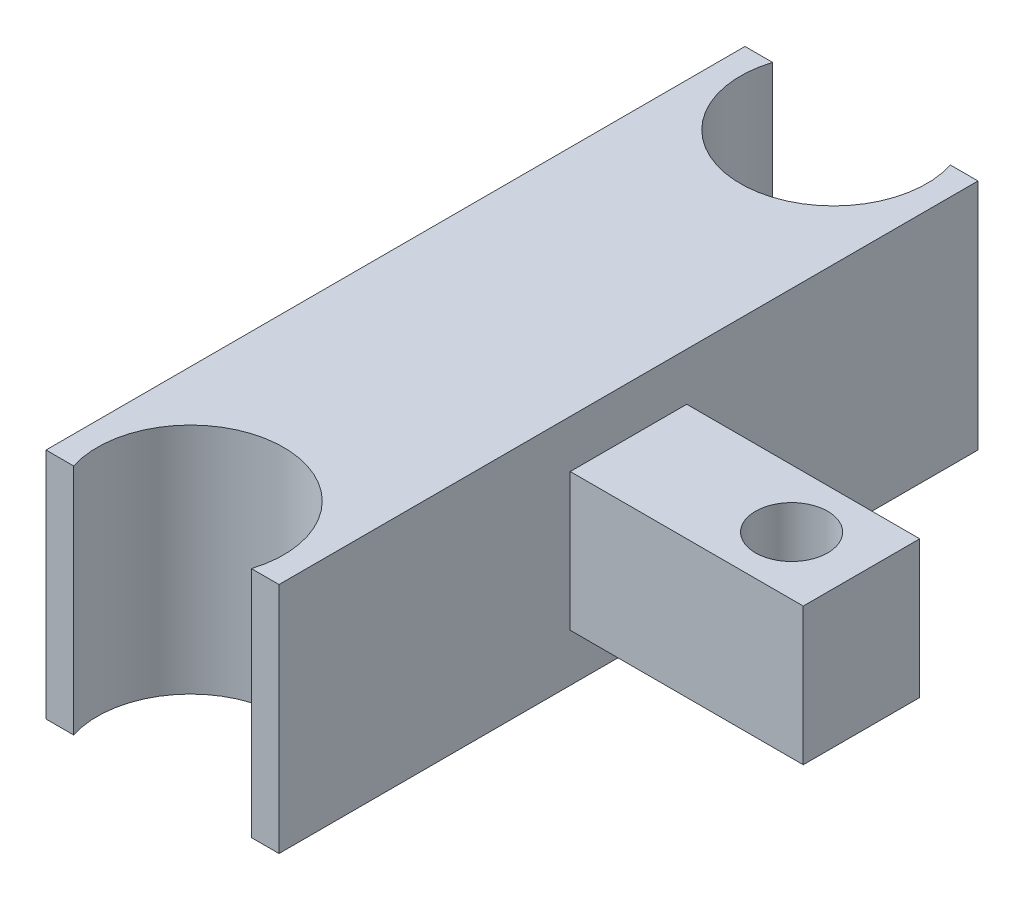
SolidWorks part; units mm, degrees
ref_plane "前视基准面" through (0, 0, 0) normal (0, 0, 1) x (1, 0, 0)
ref_plane "上视基准面" through (0, 0, 0) normal (0, 1, 0) x (1, 0, 0)
ref_plane "右视基准面" through (0, 0, 0) normal (1, 0, 0) x (0, 0, -1)
other "Configuration Table"
sketch "草图1" plane through (0, 0, 0) normal (0, 1, 0) x (1, 0, 0)
  line L1 (0, 0) -> (10, 0)
  line L2 (0, 0) -> (0, 5)
  line L3 (0, 5) -> (10, 5)
  line L4 (10, 0) -> (10, 5)
  circle A0 centre (7, 2.5) radius 1.55
  dimension "D4" = 3.1
  dimension "D1" = 5
  dimension "D2" = 10
  dimension "D3" = 3
  dimension "D5" = 2.5
extrude "凸台-拉伸1" add sketch "草图1" along normal blind 5.9
sketch "草图2" plane through (0, 0, 0) normal (-1, 0, 0) x (0, 0, 1)
  line L0 (-5, 5.9) -> (0, 0) construction
  line L1 (0, 5.9) -> (-5, 0) construction
  line L3 (12.5, -2.05) -> (-17.5, -2.05)
  line L4 (12.5, -2.05) -> (12.5, 7.95)
  line L5 (12.5, 7.95) -> (-17.5, 7.95)
  line L6 (-17.5, -2.05) -> (-17.5, 7.95)
  line L7 (12.5, -2.05) -> (-17.5, 7.95) construction
  line L8 (12.5, 7.95) -> (-17.5, -2.05) construction
  point P8 (-2.5, 2.95)
  dimension "D1" = 10
  dimension "D2" = 30
extrude "凸台-拉伸2" add sketch "草图2" along normal blind 10
sketch "草图3" plane through (0, 7.95, 0) normal (0, 1, 0) x (1, 0, 0)
  line L0 (-5, 17.5) -> (-5, -12.5) construction
  line L1 (-10, 17.5) -> (0, 17.5) construction
  line L2 (-10, -12.5) -> (0, -12.5) construction
  circle A0 centre (-5, 16.3) radius 4
  circle A1 centre (-5, -11.3) radius 4
  dimension "D2" = 8
  dimension "D3" = 8
  dimension "D1" = 1.2
  dimension "D4" = 1.2
extrude "切除-拉伸1" cut sketch "草图3" against normal blind 10 contours A0 | A1
